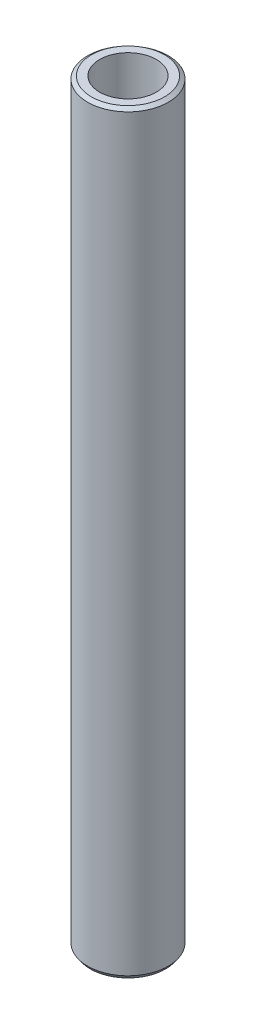
SolidWorks part; units mm, degrees
ref_plane "Front Plane" through (0, 0, 0) normal (0, 0, 1) x (1, 0, 0)
ref_plane "Top Plane" through (0, 0, 0) normal (0, 1, 0) x (1, 0, 0)
ref_plane "Right Plane" through (0, 0, 0) normal (1, 0, 0) x (0, 0, -1)
sketch "Sketch1" plane through (0, 0, 0) normal (0, 1, 0) x (1, 0, 0)
  circle A0 centre (0, 0) radius 12.5
  dimension "SHAFT_OD" = 25
extrude "Boss-Extrude1" add sketch "Sketch1" along normal blind 233.8304
sketch "Sketch2" plane through (0, 0, 0) normal (0, 1, 0) x (1, 0, 0)
  circle A0 centre (0, 0) radius 8.7872
  dimension "BORE_D" = 17.5744
extrude "Cut-Extrude1" cut sketch "Sketch2" along normal through all
chamfer "Chamfer1" distance 0.8433 angle 54.614 2 edges at (0, 233.8304, 12.5) (0, 0, 12.5) first distance on face at (0, 233.8304, 12.5) first distance on face at (0, 0, 8.7872)
